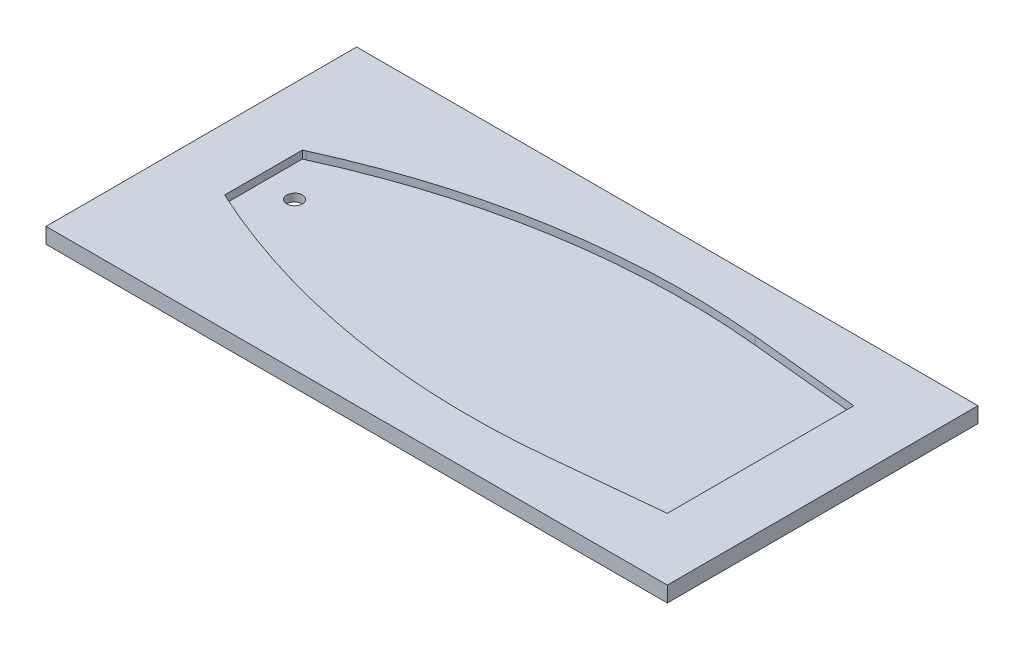
SolidWorks part; units mm, degrees
ref_plane "Front Plane" through (0, 0, 0) normal (0, 0, 1) x (1, 0, 0)
ref_plane "Top Plane" through (0, 0, 0) normal (0, 1, 0) x (1, 0, 0)
ref_plane "Right Plane" through (0, 0, 0) normal (1, 0, 0) x (0, 0, -1)
sketch "Sketch1" plane through (0, 0, 0) normal (0, 1, 0) x (1, 0, 0)
  line L1 (-127, 63.5) -> (127, 63.5)
  line L2 (-127, 63.5) -> (-127, -63.5)
  line L3 (-127, -63.5) -> (127, -63.5)
  line L4 (127, 63.5) -> (127, -63.5)
  line L5 (-127, 63.5) -> (127, -63.5) construction
  line L6 (-127, -63.5) -> (127, 63.5) construction
  point P0 (0, 0)
  dimension "D1" = 254
  dimension "D2" = 127
extrude "Boss-Extrude1" add sketch "Sketch1" along normal blind 6.35
sketch "Sketch2" plane through (0, 6.35, 0) normal (0, 1, 0) x (1, 0, 0)
  line L0 (-127, 63.5) -> (-127, -63.5) construction
  circle A0 centre (-88.9, 0) radius 3.175
  dimension "D1" = 6.35
  dimension "D2" = 38.1
extrude "Cut-Extrude1" cut sketch "Sketch2" against normal blind 6.35
sketch "Sketch5" plane through (0, 6.35, 0) normal (0, 1, 0) x (1, 0, 0)
  line L0 (-101.6, 15.875) -> (-101.6, -15.875)
  line L1 (-101.6, -15.875) -> (-25.4, -50.8)
  line L2 (-25.4, -50.8) -> (101.6, -38.1)
  line L3 (101.6, -38.1) -> (101.6, 38.1)
  line L4 (101.6, 38.1) -> (-25.4, 50.8)
  line L5 (-25.4, 50.8) -> (-101.6, 15.875)
  line L6 (127, -63.5) -> (127, 63.5) construction
  point P8 (-101.6, 0)
  point P13 (101.6, 0)
  dimension "D1" = 31.75
  dimension "D2" = 76.2
  dimension "D3" = 203.2
  dimension "D4" = 25.4
  dimension "D5" = 76.2
  dimension "D6" = 76.2
  dimension "D7" = 101.6
extrude "Cut-Extrude3" cut sketch "Sketch5" against normal blind 3.175
fillet "Fillet2" radius 304.8 2 edges at (-25.4, 4.7625, 50.8) (-25.4, 4.7625, -50.8)
